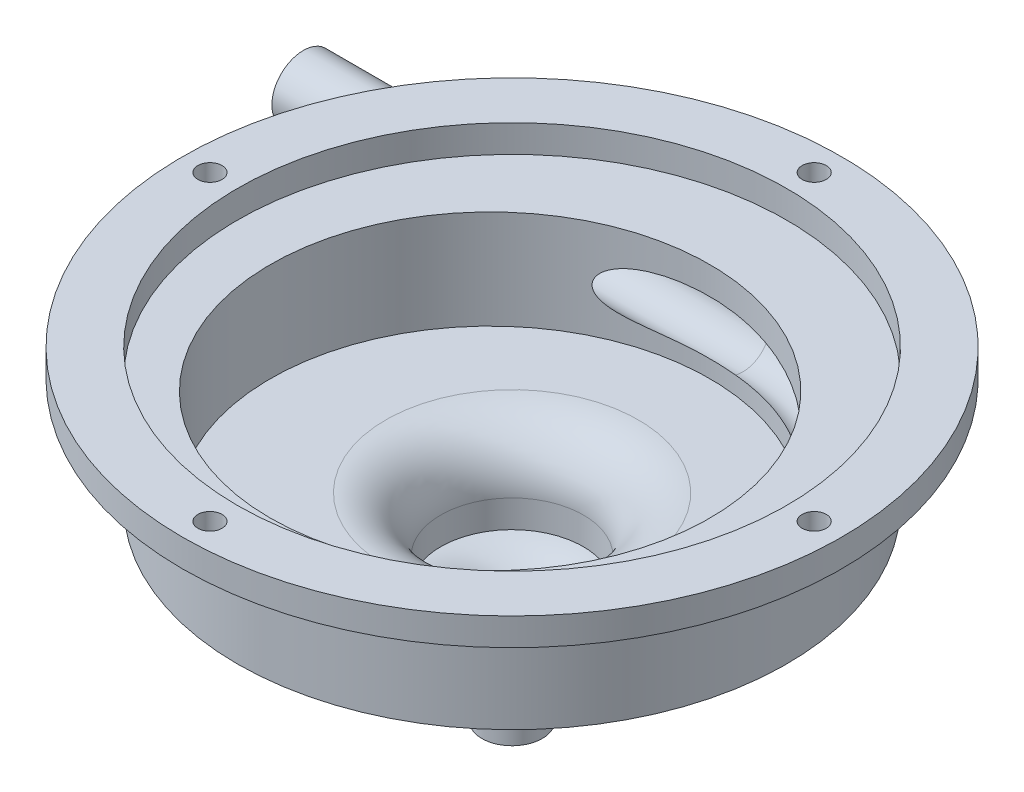
SolidWorks part; units mm, degrees
material "PLA"
ref_plane "Front Plane" through (0, 0, 0) normal (0, 0, 1) x (1, 0, 0)
ref_plane "Top Plane" through (0, 0, 0) normal (0, 1, 0) x (1, 0, 0)
ref_plane "Right Plane" through (0, 0, 0) normal (1, 0, 0) x (0, 0, -1)
sketch "Sketch1" plane through (0, 0, 0) normal (0, 1, 0) x (1, 0, 0)
  circle A0 centre (0, 0) radius 50
  circle A1 centre (0, -4) radius 40
  point P3 (0, 0)
  point P6 (0, 0)
  dimension "D1" = 4
  dimension "D2" = 80
extrude "Boss-Extrude1" add sketch "Sketch1" along normal blind 20
sketch "Sketch2" plane through (0, 0, 0) normal (0, 1, 0) x (1, 0, 0)
  circle A0 centre (0, 0) radius 50
  circle A1 centre (0, -4) radius 40
  dimension "D1" = 4
extrude "Boss-Extrude2" add sketch "Sketch2" along normal blind 2 and the other way blind 4 contours A1 region at (0, 0, 4)
sketch "Sketch3" plane through (0, 20, 0) normal (0, 1, 0) x (1, 0, 0)
  circle A0 centre (0, 0) radius 50
  circle A1 centre (0, 0) radius 60
  circle A2 centre (0, 55) radius 2.2
  circle A3 centre (55, 0) radius 2.2
  circle A4 centre (0, -55) radius 2.2
  circle A5 centre (-55, 0) radius 2.2
  point P15 (0, 0)
  dimension "D1" = 55
  dimension "D2" = 4
extrude "Boss-Extrude3" add sketch "Sketch3" along normal blind 5 separate body
ref_plane "Plane1" through (-50, 0, 0) normal (-1, 0, 0) x (0, 0, 1)
sketch "Sketch4" plane through (-50, 0, 0) normal (-1, 0, 0) x (0, 0, 1)
  circle A0 centre (-37, 10) radius 4.75
  circle A1 centre (-37, 10) radius 5.75
  point P3 (0, 0)
  point P5 (0, 0)
  point P6 (0, 0)
  dimension "D1" = 9.5
  dimension "D2" = 11.5
  dimension "D3" = 10
  dimension "D4" = 37
sketch "Sketch5" plane through (0, 0, 0) normal (0, 1, 0) x (1, 0, 0)
  line L0 (-50, 37) -> (-20.0985, 37)
  line L2 (-50, 41.75) -> (-50, 32.25) construction
  point P4 (-18.5459, 37)
  point P5 (-20.0985, 37)
  point P6 (-50, 37)
sweep "Sweep1" add profiles "Sketch4" path "Sketch5"
sketch "Sketch6" plane through (0, 0, 0) normal (0, 1, 0) x (1, 0, 0)
  line L0 (-50, 41) -> (5, 41)
  line L1 (-50, 11) -> (-50, -11) construction
  arc A0 (5, 41) -> (33.5816, -28.002) centre (5, 0.5795) cw
  point P6 (33.5816, -28.002)
  point P8 (0, 0)
  dimension "D1" = 135
  dimension "D2" = 55
  dimension "D3" = 41
sketch "Sketch7" plane through (-50, 0, 0) normal (-1, 0, 0) x (0, 0, 1)
  circle A0 centre (-37, 10.0538) radius 5
  dimension "D1" = 37
sweep "Cut-Sweep4" cut profiles "Sketch7" path "Sketch6"
sketch "Sketch8" plane through (-50, 0, 0) normal (-1, 0, 0) x (0, 0, 1)
  circle A0 centre (-36.9889, 10.0296) radius 4.9733
  circle A1 centre (-36.9889, 10.0296) radius 5.7184
extrude "Boss-Extrude4" add sketch "Sketch8" along normal blind 25
sketch "Sketch9" plane through (0, -4, 0) normal (0, -1, 0) x (1, 0, 0)
  circle A0 centre (0, 0) radius 15
extrude "Boss-Extrude5" add sketch "Sketch9" along normal blind 15
sketch "Sketch10" plane through (0, -19, 0) normal (0, -1, 0) x (1, 0, 0)
  circle A0 centre (0, 0) radius 5.5
extrude "Boss-Extrude6" add sketch "Sketch10" along normal blind 15
sketch "Sketch11" plane through (0, -34, 0) normal (0, -1, 0) x (1, 0, 0)
  circle A0 centre (0, 0) radius 4.5
extrude "Cut-Extrude1" cut sketch "Sketch11" against normal through all
sketch "Sketch12" plane through (0, 2, 0) normal (0, 1, 0) x (1, 0, 0)
  circle A0 centre (0, 0) radius 13
extrude "Cut-Extrude2" cut sketch "Sketch12" against normal blind 15
fillet "Fillet1" radius 10 2 edges at (0, -13, 4.5) (0, 2, 13)
